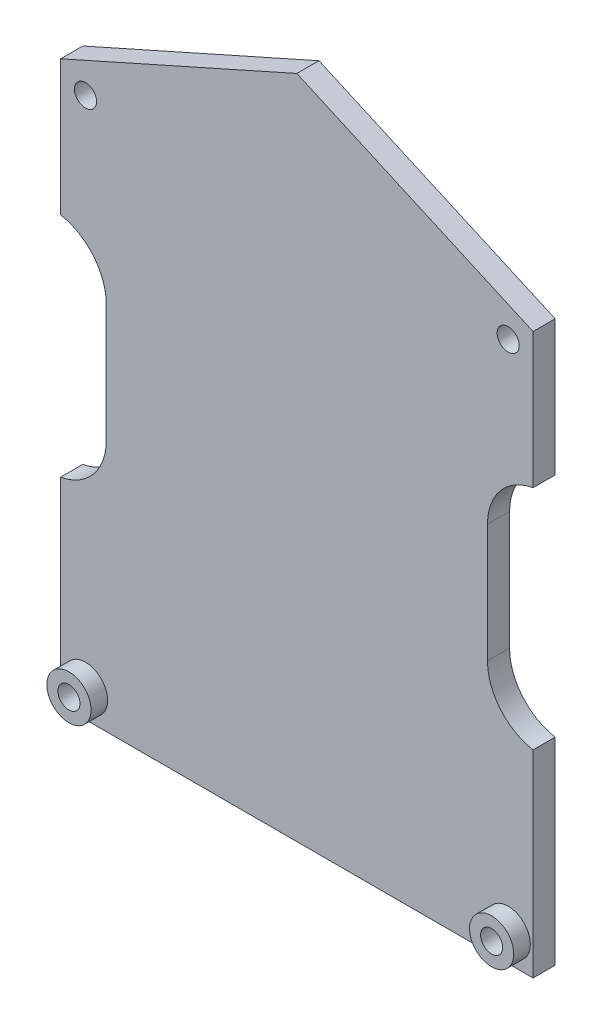
SolidWorks part; units mm, degrees
ref_plane "Front Plane" through (0, 0, 0) normal (0, 0, 1) x (1, 0, 0)
ref_plane "Top Plane" through (0, 0, 0) normal (0, 1, 0) x (1, 0, 0)
ref_plane "Right Plane" through (0, 0, 0) normal (1, 0, 0) x (0, 0, -1)
sketch "Sketch3" plane through (0, 0, 0) normal (0, 0, 1) x (1, 0, 0)
  line L0 (43.25, 0) -> (-43.25, 0) construction
  line L1 (0, 0) -> (0, 50) construction
  line L2 (67.25, 0) -> (-67.25, 0) construction
  line L3 (-67.25, 0) -> (-67.25, 20) construction
  line L4 (-67.25, 20) -> (0, 50) construction
  line L5 (67.25, 0) -> (67.25, 20) construction
  line L6 (67.25, 20) -> (0, 50) construction
  line L7 (-43.25, 8.8065) -> (0, 28.1002) construction
  line L8 (43.25, 8.8065) -> (0, 28.1002) construction
  line L9 (-43.25, 0) -> (-43.25, 8.8065) construction
  line L10 (43.25, 0) -> (43.25, 8.8065) construction
  line L11 (-59.102, 1.735) -> (0, 28.1002) construction
  line L12 (59.102, 1.735) -> (0, 28.1002) construction
  line L13 (-42.75, 8.4821) -> (-42.75, -16)
  line L15 (-42.75, 8.4821) -> (0, 27.5527)
  line L16 (-67.25, 0) -> (-67.25, -56.6) construction
  line L17 (-35, -56.6) -> (-67.25, -56.6) construction
  line L18 (-42.75, -16) -> (-34.5, -16)
  line L19 (-34.5, -16) -> (-34.5, -57.1)
  line L20 (-34.5, -57.1) -> (-42.75, -57.1)
  line L21 (-42.75, 0) -> (-42.75, 8.4821) construction
  line L22 (42.75, 0) -> (42.75, 8.4821) construction
  line L26 (-42.75, -92.85) -> (42.75, -92.85)
  line L27 (-38.25, 5) -> (-38.25, -87.85) construction
  line L28 (-67.25, -16.5) -> (-35, -16.5) construction
  line L29 (-35, -16.5) -> (-35, -56.6) construction
  line L30 (-67.25, -16) -> (-34.5, -16) construction
  line L31 (-42.75, -57.1) -> (-42.75, -92.85)
  line L32 (-34.5, -57.1) -> (-67.25, -57.1) construction
  line L33 (42.75, 8.4821) -> (0, 27.5527) construction
  line L34 (42.75, -57.1) -> (42.75, -92.85)
  line L35 (34.5, -57.1) -> (42.75, -57.1)
  line L36 (34.5, -16) -> (34.5, -57.1)
  line L37 (42.75, -16) -> (34.5, -16)
  line L38 (42.75, 8.4821) -> (42.75, -16)
  line L39 (42.75, 8.4821) -> (0, 27.5527)
  circle A4 centre (-38.25, 5) radius 2
  circle A5 centre (-38.25, -87.85) radius 2
  circle A6 centre (38.25, -87.85) radius 2
  circle A7 centre (38.25, 5) radius 2
  point P4 (0, 0)
  point P10 (0, 0)
  dimension "D16" = 4
  dimension "D17" = 5
  dimension "D18" = 5
  dimension "D19" = 5
  dimension "D20" = 8.25
  dimension "D1" = 86.5
  dimension "D2" = 50
  dimension "D3" = 134.5
  dimension "D4" = 20
  dimension "D5" = 20
  dimension "D8" = 16.5
  dimension "D9" = 92.85
  dimension "D10" = 40.1
  dimension "D11" = 0.5
  dimension "D6" = 20
  dimension "D7" = 0.5
extrude "Boss-Extrude1" add sketch "Sketch3" along normal blind 4
fillet "Fillet1" radius 10 4 edges at (34.5, -57.1, 2) (34.5, -16, 2) (-34.5, -57.1, 2) (-34.5, -16, 2)
sketch "Sketch4" plane through (0, 0, 4) normal (0, 0, 1) x (1, 0, 0)
  circle A0 centre (-38.25, -87.85) radius 2 construction
  circle A1 centre (38.25, -87.85) radius 2 construction
  circle A2 centre (-38.25, -87.85) radius 2
  circle A3 centre (38.25, -87.85) radius 2
  circle A4 centre (38.25, -87.85) radius 4
  circle A5 centre (-38.25, -87.85) radius 4
  dimension "D1" = 2
extrude "Boss-Extrude2" add sketch "Sketch4" along normal blind 3
